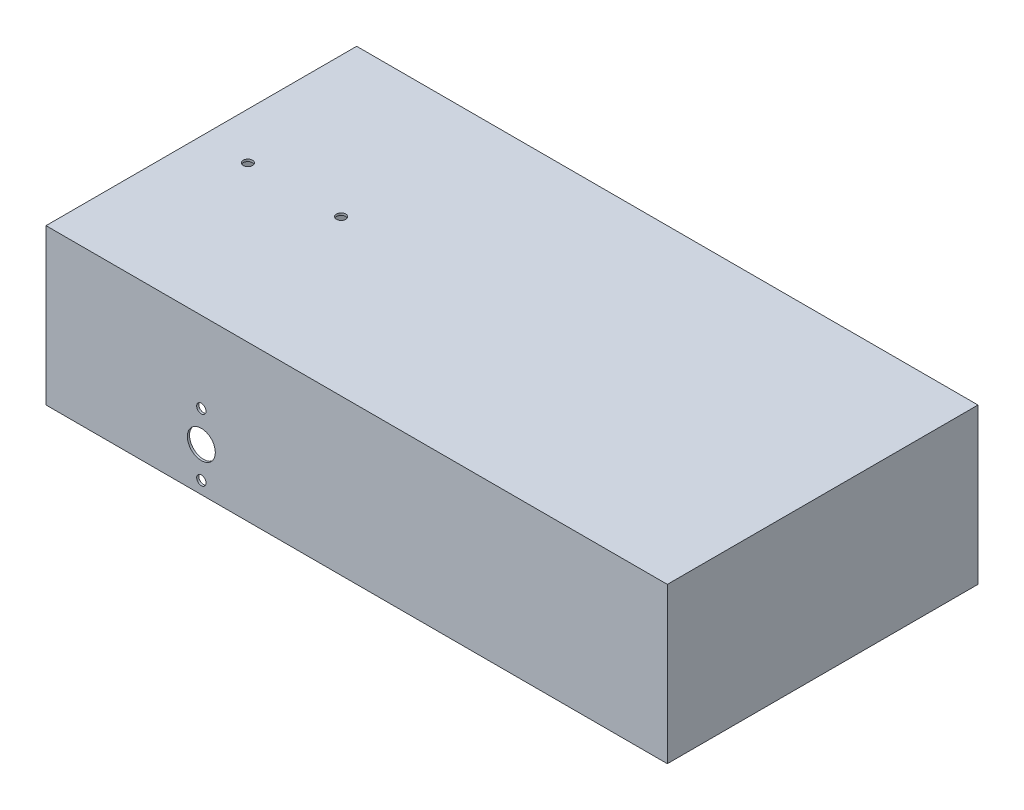
SolidWorks part; units mm, degrees
ref_plane "Front Plane" through (0, 0, 0) normal (0, 0, 1) x (1, 0, 0)
ref_plane "Top Plane" through (0, 0, 0) normal (0, 1, 0) x (1, 0, 0)
ref_plane "Right Plane" through (0, 0, 0) normal (1, 0, 0) x (0, 0, -1)
sketch "Sketch1" plane through (0, 0, 0) normal (0, 1, 0) x (1, 0, 0)
  line L1 (0, 50) -> (200, 50)
  line L2 (0, 50) -> (0, -50)
  line L3 (0, -50) -> (200, -50)
  line L4 (200, 50) -> (200, -50)
  point P4 (0, 0)
  dimension "D1" = 200
  dimension "D2" = 100
extrude "Boss-Extrude1" add sketch "Sketch1" along normal blind 50
sketch "Sketch2" plane through (0, 0, 50) normal (0, 0, 1) x (1, 0, 0)
  line L0 (0, 50) -> (0, 0) construction
  line L1 (50, 24) -> (50, 4) construction
  line L2 (0, 50) -> (200, 50) construction
  circle A0 centre (50, 14) radius 4.5
  circle A1 centre (50, 4) radius 1.5
  circle A2 centre (50, 24) radius 1.5
  point P0 (50, 14)
  point P9 (50, 14)
  dimension "D3" = 9
  dimension "D4" = 3
  dimension "D1" = 50
  dimension "D2" = 36
  dimension "D5" = 20
sketch "Sketch3" plane through (0, 0, 0) normal (0, -1, 0) x (1, 0, 0)
  line L0 (0.7, 49.3) -> (0.7, -49.3)
  line L1 (0.7, -49.3) -> (199.3, -49.3)
  line L2 (199.3, -49.3) -> (199.3, 49.3)
  line L3 (199.3, 49.3) -> (0.7, 49.3)
  line L4 (0, 50) -> (0, -50)
  line L5 (0, -50) -> (200, -50)
  line L6 (200, -50) -> (200, 50)
  line L7 (200, 50) -> (0, 50)
  line L8 (0, 50) -> (0, -50) construction
  line L9 (0, -50) -> (200, -50) construction
  line L10 (200, -50) -> (200, 50) construction
  line L11 (200, 50) -> (0, 50) construction
  dimension "D1" = 0
  dimension "D2" = 0.7
extrude "Cut-Extrude1" cut sketch "Sketch3" against normal offset from surface (49.3 mm away) 0.7 up to face at (100, 50, 0)
sketch "Sketch4" plane through (0, 0, 0) normal (0, -1, 0) x (1, 0, 0)
  line L0 (0.7, -49.3) -> (199.3, -49.3) construction
  line L1 (145, -49.3) -> (199.3, -49.3)
  line L2 (145, -49.3) -> (145, 49.3)
  line L3 (145, 49.3) -> (199.3, 49.3)
  line L4 (199.3, -49.3) -> (199.3, 49.3)
  line L5 (199.3, 49.3) -> (0.7, 49.3) construction
  line L6 (160, -47.9) -> (160, 49.3) construction
  line L7 (200, -50) -> (200, 50) construction
  line L8 (199.3, -49.3) -> (199.3, 49.3) construction
  circle A0 centre (160, 0.7) radius 11.43 construction
  point P12 (160, 0.7)
  dimension "D3" = 22.86
  dimension "D1" = 40
  dimension "D2" = 55
  dimension "D4" = 50
extrude "Boss-Extrude2" add sketch "Sketch4" against normal blind 0.7
extrude "Cut-Extrude2" cut sketch "Sketch2" against normal through all
sketch "Sketch6" plane through (0, 0, 50) normal (0, 0, 1) x (1, 0, 0)
  line L0 (4.6, 50) -> (4.6, 0) construction
  line L1 (0, 50) -> (200, 50) construction
  line L2 (200, 0) -> (0, 0) construction
  line L3 (0, 45) -> (200, 45) construction
  line L4 (0, 50) -> (0, 0) construction
  line L5 (200, 50) -> (200, 0) construction
  line L6 (0, 35) -> (200, 35) construction
  line L7 (54.1, 45) -> (54.1, 35) construction
  line L8 (69.1, 45) -> (69.1, 35) construction
  circle A0 centre (4.6, 45) radius 1.5
  circle A1 centre (4.6, 35) radius 1.5
  circle A2 centre (54.1, 45) radius 1.5
  circle A3 centre (54.1, 35) radius 1.5
  circle A4 centre (69.1, 45) radius 1.5
  circle A5 centre (69.1, 35) radius 1.5
  dimension "D1" = 3
  dimension "D3" = 5
  dimension "D4" = 10
  dimension "D5" = 4.6
  dimension "D6" = 15
  dimension "D7" = 54.1
extrude "Cut-Extrude3" [suppressed] cut sketch "Sketch6" against normal up to surface (0.7 mm away) up to face at (51.5, 4, 49.3)
sketch "Sketch7" plane through (0, 0, 0) normal (-1, 0, 0) x (0, 0, 1)
  line L0 (42, 50) -> (42, 0) construction
  line L1 (-50, 50) -> (50, 50) construction
  line L2 (-50, 0) -> (50, 0) construction
  circle A0 centre (42, 45) radius 1.5
  circle A1 centre (42, 35) radius 1.5
  dimension "D4" = 3
  dimension "D1" = 8
  dimension "D2" = 5
  dimension "D3" = 10
extrude "Cut-Extrude4" [suppressed] cut sketch "Sketch7" against normal up to surface (0.7 mm away) up to face at (0.7, 24.65, 0)
sketch "Sketch8" plane through (0, 0, 0) normal (0, -1, 0) x (1, 0, 0)
  line L0 (160, -47.9) -> (160, 49.3) construction
  circle A0 centre (160, 8.45) radius 1.21
  circle A1 centre (160, -7.05) radius 1.21
  dimension "D2" = 2.42
  dimension "D1" = 7.75
  dimension "D3" = 7.75
extrude "Cut-Extrude6" cut sketch "Sketch8" against normal up to next contours A1 | A0
sketch "Sketch9" plane through (0, 50, 0) normal (0, 1, 0) x (1, 0, 0)
  line L0 (0, 0) -> (200, 0) construction
  line L1 (200, 50) -> (200, -50) construction
  circle A0 centre (15, 0) radius 1.5
  circle A1 centre (45, 0) radius 1.5
  dimension "D1" = 3
  dimension "D2" = 15
  dimension "D3" = 30
extrude "Cut-Extrude7" cut sketch "Sketch9" against normal through all
